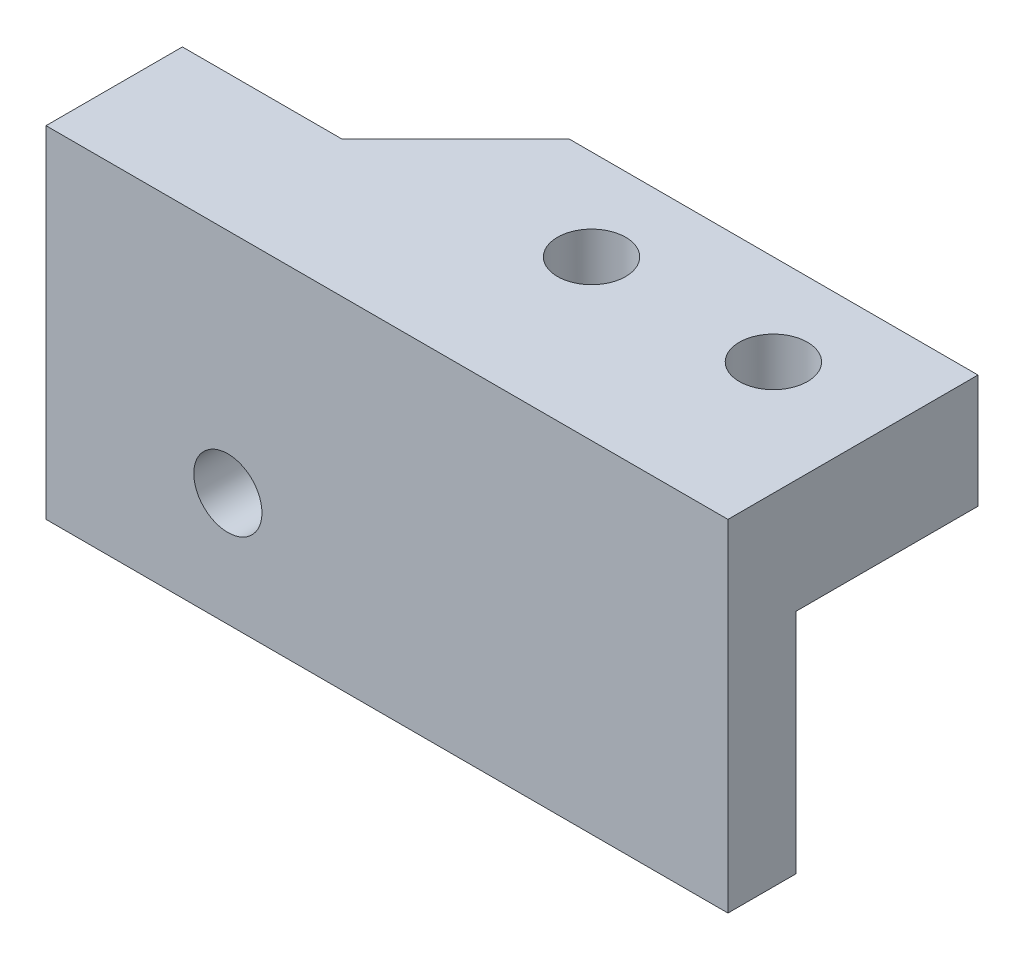
SolidWorks part; units mm, degrees
ref_plane "前视基准面" through (0, 0, 0) normal (0, 0, 1) x (1, 0, 0)
ref_plane "上视基准面" through (0, 0, 0) normal (0, 1, 0) x (1, 0, 0)
ref_plane "右视基准面" through (0, 0, 0) normal (1, 0, 0) x (0, 0, -1)
sketch "草图1" plane through (0, 0, 0) normal (0, 0, 1) x (1, 0, 0)
  line L1 (0, 0) -> (30, 0)
  line L2 (0, 0) -> (0, 15)
  line L3 (0, 15) -> (30, 15)
  line L4 (30, 0) -> (30, 15)
  circle A0 centre (8, 5) radius 1.5
  dimension "D5" = 3
  dimension "D1" = 30
  dimension "D2" = 15
  dimension "D3" = 8
  dimension "D4" = 5
extrude "凸台-拉伸1" add sketch "草图1" along normal blind 11
sketch "草图2" plane through (0, 0, 0) normal (0, -1, 0) x (1, 0, 0)
  line L0 (30, 11) -> (30, 0) construction
  line L1 (0, 0) -> (30, 0) construction
  circle A0 centre (25, 4) radius 1.5
  circle A1 centre (17, 4) radius 1.5
  point P6 (0, 0)
  point P8 (0, 0)
  dimension "D3" = 3
  dimension "D1" = 5
  dimension "D2" = 8
  dimension "D4" = 4
extrude "切除-拉伸1" cut sketch "草图2" against normal blind 20
sketch "草图3" plane through (0, 0, 0) normal (0, -1, 0) x (1, 0, 0)
  line L1 (0, 0) -> (12, 0)
  line L2 (0, 0) -> (0, 5)
  line L3 (0, 5) -> (12, 5)
  line L4 (12, 0) -> (12, 5)
  circle A0 centre (17, 4) radius 1.5 construction
  dimension "D1" = 5
  dimension "D2" = 5
extrude "切除-拉伸2" cut sketch "草图3" against normal blind 20
sketch "草图5" plane through (0, 0, 0) normal (0, -1, 0) x (1, 0, 0)
  line L0 (30, 11) -> (30, 0) construction
  line L1 (12, 0) -> (30, 0)
  line L2 (12, 0) -> (12, 8)
  line L3 (12, 8) -> (30, 8)
  line L4 (30, 0) -> (30, 8)
  dimension "D1" = 8
extrude "切除-拉伸3" cut sketch "草图5" against normal blind 10
chamfer "倒角1" distance 5 angle 45 1 edges at (12, 12.5, 5)
